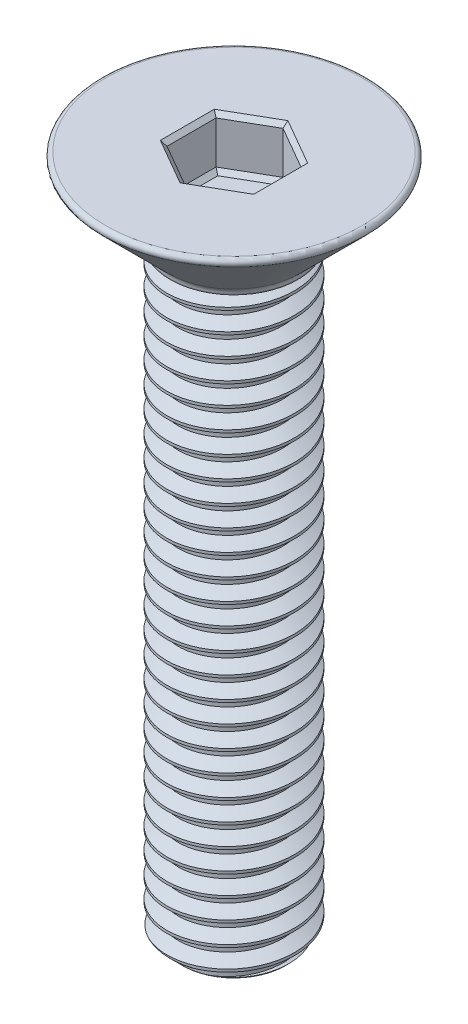
SolidWorks part; units mm, degrees
material "AISI Type A2 Tool Steel"
ref_plane "Front Plane" through (0, 0, 0) normal (0, 0, 1) x (1, 0, 0)
ref_plane "Top Plane" through (0, 0, 0) normal (0, 1, 0) x (1, 0, 0)
ref_plane "Right Plane" through (0, 0, 0) normal (1, 0, 0) x (0, 0, -1)
sketch "Sketch1" plane through (0, 0, 0) normal (0, 1, 0) x (1, 0, 0)
  circle A0 centre (0, 0) radius 1.5
  dimension "D1" = 3
extrude "Boss-Extrude1" add sketch "Sketch1" along normal blind 14.14
thread "Thread1" pitch 0.5 method cut profile "Thread Profile1" start angle 0, offset 1, length 0, pitch 0.5, diameter 3
ref_plane "Plane1" through (-1.5, 15.14, 0) normal (0, 0, 1) x (-1, 0, 0)
sketch "Thread Profile1" plane through (-1.5, 15.14, 0) normal (0, 0, 1) x (-1, 0, 0)
  line L0 (0, 0) -> (0, 0.5) construction
  line L11 (0, 0) -> (0, 0.4375)
  line L12 (0, 0.4375) -> (-0.2706, 0.2812)
  line L13 (-0.2706, 0.2812) -> (-0.2706, 0.1562)
  line L15 (-0.2706, 0.1562) -> (0, 0)
  line L17 (-0.2706, 0.2187) -> (0, 0.2187) construction
  point P2 (0, 0)
  dimension "Pitch" = 0.5
  dimension "Profile_Angle" = 60
  dimension "Profile_Land" = 0.125
  dimension "Profile_Height" = 0.2706
sketch "Sketch5" plane through (0, 14.14, 0) normal (0, 1, 0) x (1, 0, 0)
  circle A0 centre (0, 0) radius 1.5
  dimension "D1" = 3
extrude "Boss-Extrude2" add sketch "Sketch5" along normal blind 0.1
sketch "Sketch6" plane through (0, 14.24, 0) normal (0, 1, 0) x (1, 0, 0)
  circle A0 centre (0, 0) radius 1.5
  dimension "D1" = 3
extrude "Boss-Extrude3" add sketch "Sketch6" along normal blind 1.76 draft 45 draft outward yes
sketch "Sketch7" plane through (0, 0, 0) normal (0, 0, 1) x (1, 0, 0)
  line L0 (0, 0) -> (0, 0.1997) construction
  line L1 (0, 0) -> (1.51, 0) construction
  line L2 (1.51, 0) -> (1.51, 0.3)
  line L3 (1.51, 0.3) -> (1.21, 0)
  line L4 (1.21, 0) -> (1.51, 0)
  dimension "D1" = 45
  dimension "D2" = 0.3
  dimension "D3" = 1.51
revolve "Cut-Revolve1" cut sketch "Sketch7" angle 360 about L0
fillet "Fillet1" radius 0.1 1 edges at (0, 16, 3.26)
fillet "Fillet2" radius 0.2 1 edges at (0, 14.24, 1.5)
sketch "Sketch8" plane through (0, 16, 0) normal (0, 1, 0) x (1, 0, 0)
  line L1 (0, 1.1547) -> (-1, 0.5774)
  line L2 (-1, 0.5774) -> (-1, -0.5774)
  line L3 (-1, -0.5774) -> (0, -1.1547)
  line L4 (0, -1.1547) -> (1, -0.5774)
  line L5 (1, -0.5774) -> (1, 0.5774)
  line L6 (1, 0.5774) -> (0, 1.1547)
  circle A0 centre (0, 0) radius 1 construction
  dimension "D1" = 2
extrude "Cut-Extrude1" cut sketch "Sketch8" against normal blind 1.1
chamfer "Chamfer1" distance 0.1 angle 45 6 edges at (-1, 16, 0) (-0.5, 16, 0.866) (0.5, 16, 0.866) (1, 16, 0) (0.5, 16, -0.866) (-0.5, 16, -0.866)
sketch "Sketch9" plane through (0, 14.9, 0) normal (0, 1, 0) x (1, 0, 0)
  line L1 (0, 1.1547) -> (-1, 0.5774)
  line L2 (-1, 0.5774) -> (-1, -0.5774)
  line L3 (-1, -0.5774) -> (0, -1.1547)
  line L4 (0, -1.1547) -> (1, -0.5774)
  line L5 (1, -0.5774) -> (1, 0.5774)
  line L6 (1, 0.5774) -> (0, 1.1547)
  circle A0 centre (0, 0) radius 1 construction
extrude "Cut-Extrude2" cut sketch "Sketch9" against normal blind 0.1 draft 45
